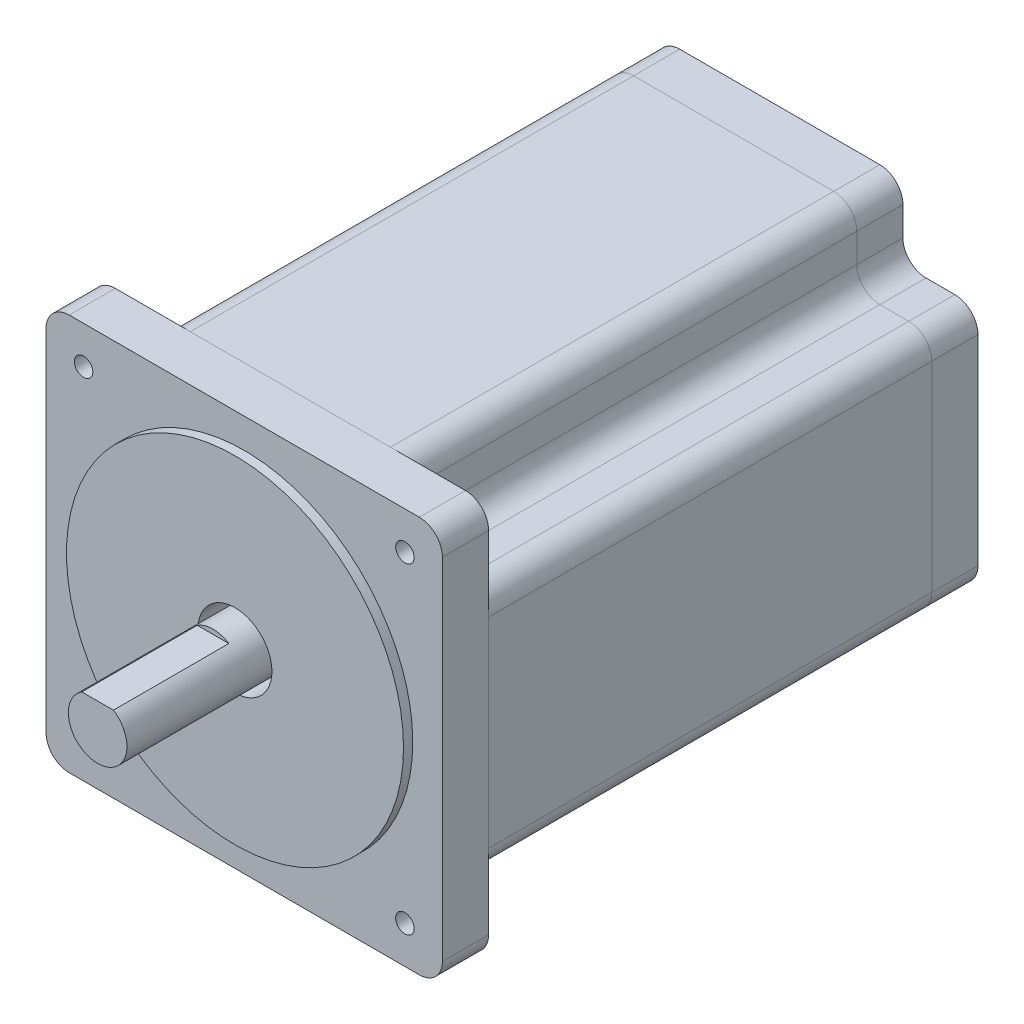
SolidWorks part; units mm, degrees
ref_plane "Płaszczyzna przednia" through (0, 0, 0) normal (0, 0, 1) x (1, 0, 0)
ref_plane "Płaszczyzna górna" through (0, 0, 0) normal (0, 1, 0) x (1, 0, 0)
ref_plane "Płaszczyzna prawa" through (0, 0, 0) normal (1, 0, 0) x (0, 0, -1)
sketch "Szkic1" plane through (0, 0, 0) normal (0, 0, 1) x (1, 0, 0)
  line L1 (42.925, -42.925) -> (-42.925, -42.925)
  line L2 (42.925, -42.925) -> (42.925, 42.925)
  line L3 (42.925, 42.925) -> (-42.925, 42.925)
  line L4 (-42.925, -42.925) -> (-42.925, 42.925)
  line L5 (42.925, -42.925) -> (-42.925, 42.925) construction
  line L6 (42.925, 42.925) -> (-42.925, -42.925) construction
  point P0 (0, 0)
  dimension "D1" = 85.85
  dimension "D2" = 85.85
extrude "Dodanie-wyciągnięcie2" add sketch "Szkic1" along normal blind 116 contours L3 L4 L1 L2
sketch "Szkic3" plane through (0, 0, 116) normal (0, 0, 1) x (1, 0, 0)
  circle A0 centre (0, 0) radius 36.5
extrude "Dodanie-wyciągnięcie3" add sketch "Szkic3" along normal blind 2
sketch "Szkic5" plane through (0, 0, 0) normal (0, 0, -1) x (-1, 0, 0)
  line L1 (-42.925, 42.925) -> (-26.675, 42.925)
  line L2 (-42.925, 42.925) -> (-42.925, 26.675)
  line L3 (-42.925, 26.675) -> (-26.675, 26.675)
  line L4 (-26.675, 42.925) -> (-26.675, 26.675)
  dimension "D1" = 16.25
  dimension "D2" = 16.25
extrude "Wytnij-wyciągnięcie1" cut sketch "Szkic5" against normal blind 106
pattern_linear "Szyk liniowy1" count 2 spacing 69.6 along (-1, 0, 0) count 2 spacing 69.6 along (0, -1, 0) of "Wytnij-wyciągnięcie1"
sketch "Szkic6" plane through (0, 0, 116) normal (0, 0, 1) x (1, 0, 0)
  line L0 (42.925, 42.925) -> (-42.925, 42.925) construction
  line L1 (-42.925, -42.925) -> (-42.925, 42.925) construction
  circle A0 centre (-34.8, 34.8) radius 2
  dimension "D1" = 8.125
  dimension "D2" = 8.125
extrude "Wytnij-wyciągnięcie2" cut sketch "Szkic6" against normal blind 10
pattern_linear "Szyk liniowy2" count 2 spacing 69.6 along (1, 0, 0) count 2 spacing 69.6 along (0, -1, 0) of "Wytnij-wyciągnięcie2"
sketch "Szkic7" plane through (0, 0, 118) normal (0, 0, 1) x (1, 0, 0)
  circle A0 centre (0, 0) radius 6.35
extrude "Dodanie-wyciągnięcie4" add sketch "Szkic7" along normal blind 29.75
sketch "Szkic8" plane through (0, 0, 118) normal (0, 0, 1) x (1, 0, 0)
  circle A0 centre (0, 0) radius 6.35
  circle A1 centre (0, 0) radius 8
extrude "Wytnij-wyciągnięcie5" cut sketch "Szkic8" against normal blind 10
sketch "Szkic10" plane through (0, 0, 147.75) normal (0, 0, 1) x (1, 0, 0)
  line L1 (-4.0051, 6.35) -> (3.6084, 6.35)
  line L2 (-4.0051, 6.35) -> (-4.0051, 5.35)
  line L3 (-4.0051, 5.35) -> (3.6084, 5.35)
  line L4 (3.6084, 6.35) -> (3.6084, 5.35)
  circle A0 centre (0, 0) radius 6.35 construction
extrude "Wytnij-wyciągnięcie6" cut sketch "Szkic10" against normal blind 25
fillet "Zaokrąglenie1" radius 5 4 edges at (-42.925, -42.925, 111) (42.925, -42.925, 111) (-42.925, 42.925, 111) (42.925, 42.925, 111)
fillet "Zaokrąglenie2" radius 5 8 edges at (42.925, -26.675, 53) (-42.925, 26.675, 53) (26.675, -42.925, 53) (-26.675, -42.925, 53) (-42.925, -26.675, 53) (-26.675, 42.925, 53) (26.675, 42.925, 53) (42.925, 26.675, 53)
fillet "Zaokrąglenie3" radius 5 4 edges at (26.675, -26.675, 53) (26.675, 26.675, 53) (-26.675, 26.675, 53) (-26.675, -26.675, 53)
sketch "Szkic14" plane through (-42.925, 0, 0) normal (-1, 0, 0) x (0, 0, 1)
  line L0 (106, 42.925) -> (106, -42.925)
split line "Linia podziałowa1"
sketch "Szkic20" plane through (0, 42.925, 0) normal (0, 1, 0) x (1, 0, 0)
  line L0 (-53.5046, -10) -> (51.8443, -10)
  line L1 (21.675, 0) -> (-21.675, 0) construction
  dimension "D1" = 10
split line "Linia podziałowa2"
